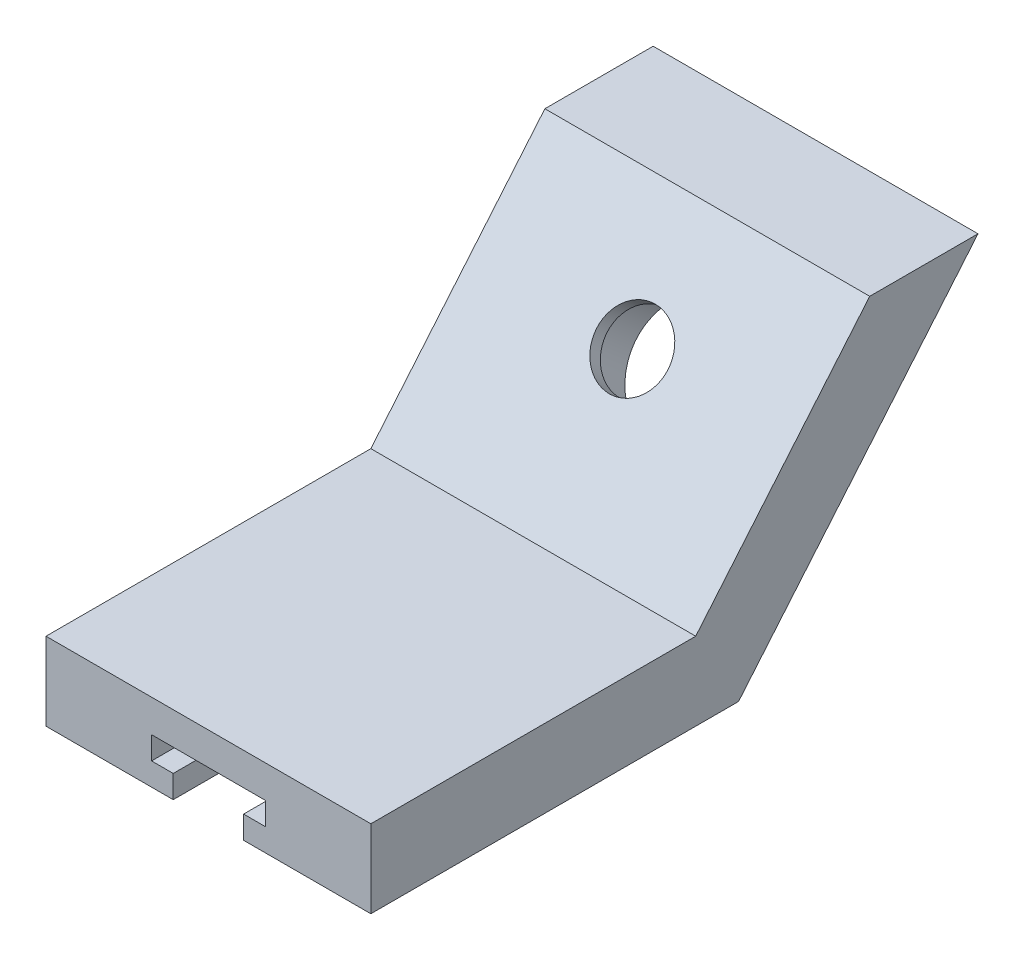
SolidWorks part; units mm, degrees
material "PLA Black"
ref_plane "Front" through (0, 0, 0) normal (0, 0, 1) x (1, 0, 0)
ref_plane "Top" through (0, 0, 0) normal (0, 1, 0) x (1, 0, 0)
ref_plane "Right" through (0, 0, 0) normal (1, 0, 0) x (0, 0, -1)
sketch "Sketch1" plane through (0, 0, 0) normal (0, 0, 1) x (1, 0, 0)
  line L0 (-5.25, -3) -> (-5.25, -5.1)
  line L1 (-5.25, -5.1) -> (-3.25, -5.1)
  line L2 (-3.25, -5.1) -> (-3.25, -7.2)
  line L3 (-3.25, -7.2) -> (-15, -7.2)
  line L4 (-15, -7.2) -> (-15, 0)
  line L5 (0, 4.4243) -> (0, -4.5871) construction
  line L6 (3.25, -7.2) -> (15, -7.2)
  line L7 (5.25, -5.1) -> (3.25, -5.1)
  line L8 (3.25, -5.1) -> (3.25, -7.2)
  line L9 (5.25, -3) -> (5.25, -5.1)
  line L10 (15, -7.2) -> (15, 0)
  line L11 (-15, 0) -> (15, 0)
  line L12 (5.25, -3) -> (-5.25, -3)
  dimension "D1" = 2.1
  dimension "D2" = 6.5
  dimension "D3" = 3
  dimension "D4" = 30
  dimension "D5" = 10.5
extrude "Boss-Extrude1" add sketch "Sketch1" along normal blind 30
sketch "Sketch3" plane through (15, 0, 0) normal (1, 0, 0) x (0, 0, -1)
  line L0 (0, 0) -> (16.0697, 19.1511)
  line L1 (16.0697, 19.1511) -> (26.0697, 19.1511)
  line L2 (26.0697, 19.1511) -> (3.9585, -7.2)
  line L3 (3.9585, -7.2) -> (0, -7.2)
  line L5 (0, 0) -> (0, -7.2)
  dimension "D1" = 50
  dimension "D2" = 10
  dimension "D3" = 25
extrude "Boss-Extrude3" add sketch "Sketch3" against normal up to surface (30 mm away) up to face at (-15, -3.6, 15)
hole_wizard "CBORE for M6 Hex Socket Head Cap Screw1" positions "Sketch5" profile "Sketch6" counterbore size "M6" standard "DIN" end condition through all
sketch "Sketch5" plane through (0, -4.924, -5.8682) normal (0, -0.6428, -0.766) x (-1, 0, 0)
  line L0 (0, 0) -> (0, 35.9415) construction
  line L2 (-17.6898, 14.2284) -> (17.6898, 14.2284) construction
  line L4 (15, 31.4279) -> (-15, 31.4279) construction
  line L5 (15, -2.9711) -> (-15, -2.9711) construction
  point P0 (0, 14.2284)
sketch "Sketch6" plane through (0, 5.9756, -15.0141) normal (1, 0, 0) x (0, 0.766, -0.6428)
  line L0 (0, 0) -> (0, 42.9519)
  line L1 (0, 42.9519) -> (3.3, 42.9519)
  line L3 (3.3, 42.9519) -> (3.3, 6.4)
  line L4 (5.5, 6.4) -> (3.3, 6.4)
  line L5 (5.5, 6.4) -> (5.5, 0.025)
  line L6 (5.5, 0.025) -> (5.525, 0)
  line L7 (5.525, 0) -> (0, 0)
  line L8 (-5.5, 0.025) -> (-5.525, 0) construction
  line L11 (0, -6.35) -> (0, 107.95) construction
  dimension "Thru Hole Dia." = 6.6
  dimension "Thru Hole Depth" = 42.9519
  dimension "C'Bore Dia." = 11
  dimension "C'Bore Depth" = 6.4
  dimension "Near C'Sink Dia." = 11.05
  dimension "Near C'Sink Angle" = 90
